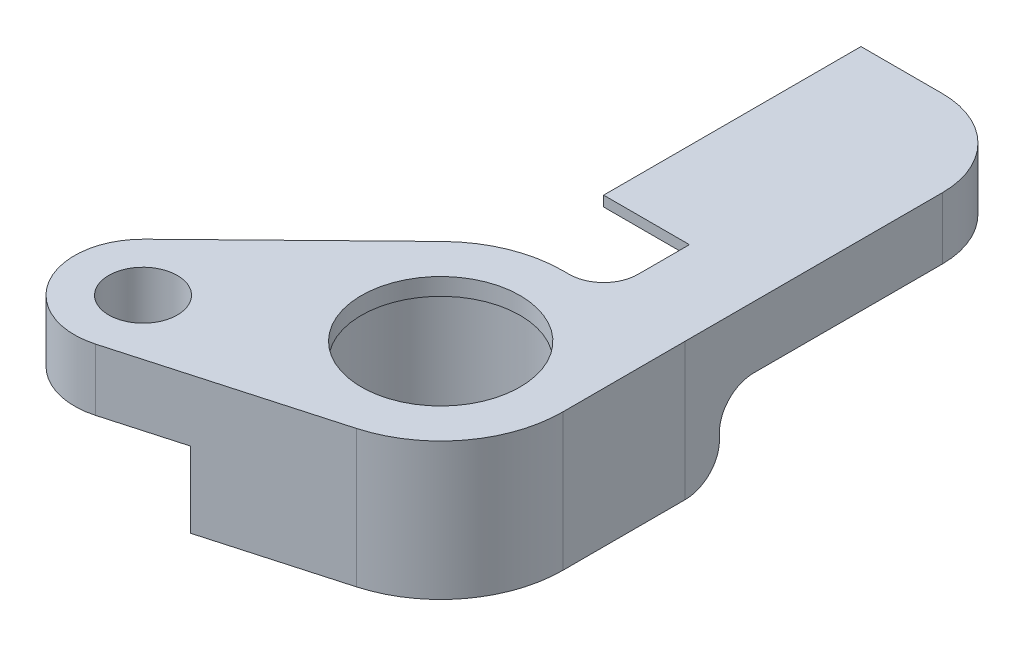
SolidWorks part; units mm, degrees
ref_plane "Front Plane" through (0, 0, 0) normal (0, 0, 1) x (1, 0, 0)
ref_plane "Top Plane" through (0, 0, 0) normal (0, 1, 0) x (1, 0, 0)
ref_plane "Right Plane" through (0, 0, 0) normal (1, 0, 0) x (0, 0, -1)
sketch "Sketch1" plane through (0, 0, 0) normal (0, 1, 0) x (1, 0, 0)
  line L0 (0, 0) -> (22, 12.7017) construction
  line L1 (22, 12.7017) -> (22, 56.9517) construction
  line L2 (0, 0) -> (22, 0) construction
  line L4 (22, 26.9517) -> (2, 26.9517) construction
  line L5 (22, 26.9517) -> (22, 66.9517) construction
  line L6 (22, 66.9517) -> (2, 66.9517) construction
  line L7 (2, 26.9517) -> (2, 66.9517) construction
  circle A0 centre (0, 0) radius 11
  circle A1 centre (22, 12.7017) radius 11.25
  dimension "D2" = 22
  dimension "D3" = 22.5
  dimension "D1" = 22
  dimension "D4" = 44.25
  dimension "D5" = 30
  dimension "D6" = 20
  dimension "D7" = 10
  dimension "D8" = 30
sketch "Sketch2" plane through (0, 0, 0) normal (0, 1, 0) x (1, 0, 0)
  line L0 (26.7433, 26.9517) -> (22, 26.9517)
  line L1 (12.0578, 22.9103) -> (-5.5816, 5.7311)
  line L3 (2.1725, -7.6994) -> (25.8698, -1.0128)
  line L4 (36.25, 12.7084) -> (36.2433, 26.9517)
  line L5 (22, 26.9517) -> (2, 26.9517) construction
  line L11 (36.25, 12.7084) -> (33.25, 12.707) construction
  line L13 (26.7433, 26.9517) -> (26.7433, 66.9517)
  line L14 (22, 66.9517) -> (2, 66.9517) construction
  line L15 (26.7433, 66.9517) -> (36.2433, 66.9517)
  line L16 (36.2433, 66.9517) -> (36.2433, 26.9517)
  arc A0 (-5.5816, 5.7311) -> (2.1725, -7.6994) centre (0, 0) ccw
  arc A1 (22, 26.9517) -> (12.0578, 22.9103) centre (22, 12.7017) ccw
  arc A2 (25.8698, -1.0128) -> (36.25, 12.7084) centre (22, 12.7017) ccw
  circle A3 centre (22, 12.7017) radius 11.25 construction
  dimension "D1" = 3
  dimension "D3" = 8
  dimension "D4" = 4.7433
  dimension "D2" = 9.5
extrude "Boss-Extrude1" add sketch "Sketch2" along normal blind 16
sketch "Sketch13" plane through (0, 0, 0) normal (0, -1, 0) x (1, 0, 0)
  circle A0 centre (22, -12.7017) radius 11.25 construction
  circle A1 centre (22, -12.7017) radius 11.25
extrude "Cut-Extrude5" cut sketch "Sketch13" against normal blind 14
sketch "Sketch14" plane through (0, 0, 0) normal (0, -1, 0) x (1, 0, 0)
  circle A0 centre (0, 0) radius 12
  circle A2 centre (0, 0) radius 11 construction
  dimension "D1" = 1
extrude "Cut-Extrude6" cut sketch "Sketch14" against normal blind 8.8
sketch "Sketch15" plane through (0, 14, 0) normal (0, -1, 0) x (1, 0, 0)
  circle A0 centre (22, -12.7017) radius 9.25
  circle A1 centre (22, -12.7017) radius 11.25 construction
  dimension "D1" = 2
extrude "Cut-Extrude7" cut sketch "Sketch15" against normal through all
sketch "Sketch17" plane through (0, 8.8, 0) normal (0, -1, 0) x (1, 0, 0)
  circle A0 centre (0, 0) radius 4
  dimension "D1" = 8
extrude "Cut-Extrude8" cut sketch "Sketch17" against normal through all
fillet "Fillet1" radius 4 1 edges at (26.7433, 8, -26.9517)
sketch "Sketch18" plane through (0, 16, 0) normal (0, 1, 0) x (1, 0, 0)
  line L0 (26.7433, 66.9517) -> (16.7433, 66.9517)
  line L1 (16.7433, 66.9517) -> (16.7433, 36.9517)
  line L2 (16.7433, 36.9517) -> (26.7433, 36.9517)
  line L3 (26.7433, 66.9517) -> (26.7433, 30.9517) construction
  line L4 (26.7433, 36.9517) -> (26.7433, 66.9517)
  dimension "D1" = 10
  dimension "D2" = 30
extrude "Boss-Extrude2" add sketch "Sketch18" against normal blind 1.2
sketch "Sketch19" plane through (0, 0, 0) normal (0, -1, 0) x (1, 0, 0)
  line L1 (36.2433, -66.9517) -> (26.7433, -66.9517)
  line L2 (36.2433, -66.9517) -> (36.2433, -30.9517)
  line L3 (36.2433, -30.9517) -> (26.7433, -30.9517)
  line L4 (26.7433, -66.9517) -> (26.7433, -30.9517)
extrude "Cut-Extrude9" cut sketch "Sketch19" against normal offset from surface (8.8 mm away) 6 up to face at (21.7433, 14.8, -51.9517)
fillet "Fillet2" radius 4 2 edges at (31.4933, 0, -30.9517) (31.4933, 8.8, -30.9517)
fillet "Fillet3" radius 10 1 edges at (36.2433, 12.4, -66.9517)
